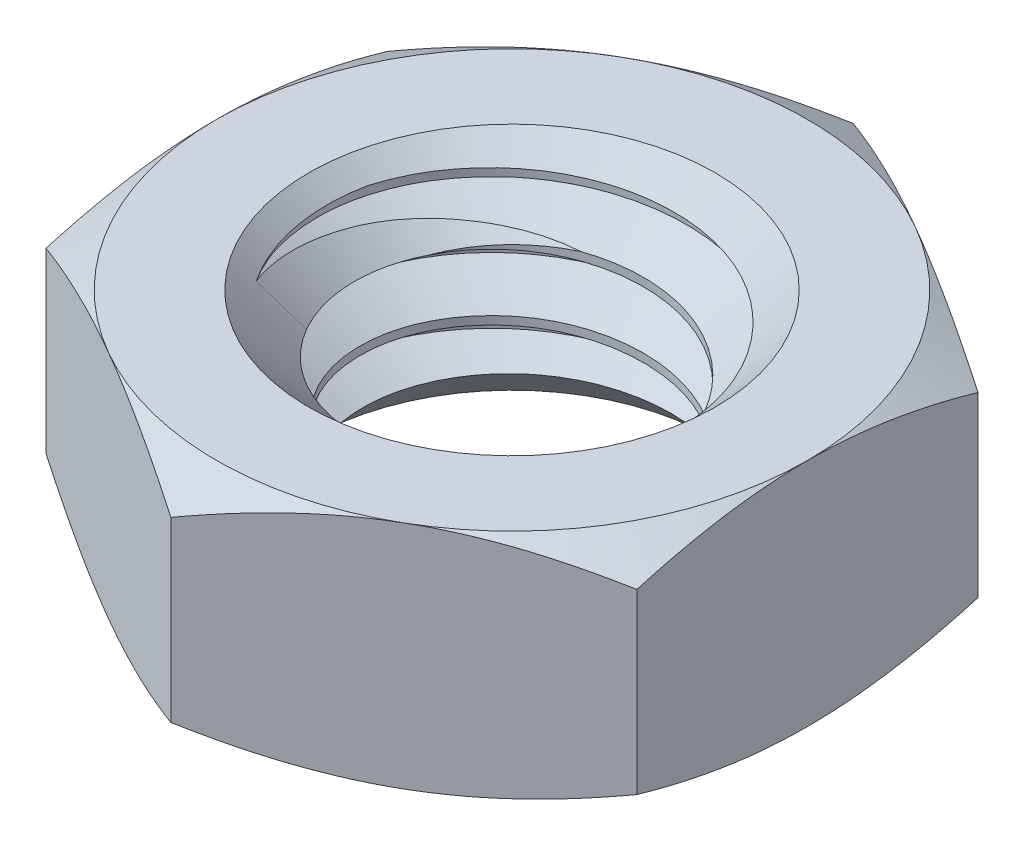
SolidWorks part; units mm, degrees
ref_plane "Front Plane" through (0, 0, 0) normal (0, 0, 1) x (1, 0, 0)
ref_plane "Top Plane" through (0, 0, 0) normal (0, 1, 0) x (1, 0, 0)
ref_plane "Right Plane" through (0, 0, 0) normal (1, 0, 0) x (0, 0, -1)
sketch "Sketch1" plane through (0, 0, 0) normal (0, 0, 1) x (1, 0, 0)
  line L0 (0, -2.4765) -> (0, 2.4765) construction
  line L1 (3.9688, 2.4765) -> (-3.9688, 2.4765) construction
  line L2 (-6.35, -2.4765) -> (6.35, -2.4765) construction
  line L3 (3.9688, 2.4765) -> (3.9687, 1.0654) construction
  point P4 (0, 0)
  point P8 (0, 2.4765)
  point P10 (0, -2.4765)
  dimension "Height" = 4.953
  dimension "Width" = 12.7
  dimension "Thread Dia" = 7.9375
  dimension "Pitch" = 1.4111
sketch "Sketch2" plane through (0, 0, 0) normal (0, 1, 0) x (1, 0, 0)
  line L1 (0, 7.3323) -> (-6.35, 3.6662)
  line L2 (-6.35, 3.6662) -> (-6.35, -3.6662)
  line L3 (-6.35, -3.6662) -> (0, -7.3323)
  line L4 (0, -7.3323) -> (6.35, -3.6662)
  line L5 (6.35, -3.6662) -> (6.35, 3.6662)
  line L6 (6.35, 3.6662) -> (0, 7.3323)
  circle A0 centre (0, 0) radius 6.35 construction
  circle A1 centre (0, 0) radius 3.9688
  point P11 (0, -3.9688)
  point P14 (0, 0)
extrude "Boss-Extrude1" add sketch "Sketch2" along normal up to vertex (2.4765 mm away) and the other way up to vertex (2.4765 mm away) up to point (0, 2.4765, 0) other way up to point (0, -2.4765, 0)
sketch "Sketch3" plane through (0, 0, 0) normal (1, 0, 0) x (0, 0, -1)
  line L0 (-7.3323, 1.9093) -> (-6.35, 2.4765)
  line L1 (-7.3323, 2.4765) -> (-7.3323, -2.4765) construction
  line L2 (-7.3323, 2.4765) -> (-3.6662, 2.4765) construction
  line L3 (-7.3323, -1.9093) -> (-6.35, -2.4765)
  line L4 (-7.3323, -2.4765) -> (-3.6662, -2.4765) construction
  line L5 (-7.3323, 1.9093) -> (-7.3323, 2.4765)
  line L6 (-7.3323, 2.4765) -> (-6.35, 2.4765)
  line L7 (-7.3323, -1.9093) -> (-7.3323, -2.4765)
  line L8 (-7.3323, -2.4765) -> (-6.35, -2.4765)
  line L9 (-6.35, 2.4765) -> (-6.35, -2.4765) construction
  line L10 (-4.3656, 2.4765) -> (-3.9688, 2.4765)
  line L11 (-3.6662, 2.4765) -> (3.6662, 2.4765) construction
  line L12 (-3.9688, 2.4765) -> (-3.9688, 2.0796)
  line L13 (-3.9688, 2.0796) -> (-4.3656, 2.4765)
  line L14 (-4.3656, -2.4765) -> (-3.9687, -2.4765)
  line L15 (-3.6662, -2.4765) -> (3.6662, -2.4765) construction
  line L16 (-3.9687, -2.4765) -> (-3.9688, -2.0796)
  line L17 (-4.3656, -2.4765) -> (-3.9688, -2.0796)
  line L18 (-3.9688, 2.0796) -> (-3.9688, -2.0796) construction
  line L19 (3.9688, 0) -> (-3.9688, 0) construction
  line L22 (0, 2.4765) -> (0, -2.4765) construction
  point P15 (-6.35, 0)
  point P24 (-3.9688, 0)
  dimension "D1" = 30
  dimension "D2" = 4.3656
revolve "Cut-Revolve1" cut sketch "Sketch3" angle 360 about L22
sketch "Sketch4" plane through (0, 2.4765, 0) normal (0, 1, 0) x (1, 0, 0)
  circle A0 centre (0, 0) radius 3.9688 construction
  circle A1 centre (0, 0) radius 3.9688
extrude "Boss-Extrude2" add sketch "Sketch4" against normal up to surface (4.953 mm away) separate body up to face at (0, -2.4765, 4.3656)
sketch "Sketch5" plane through (0, 2.4765, 0) normal (0, 1, 0) x (1, 0, 0)
  circle A0 centre (0, 0) radius 3.9688 construction
  circle A1 centre (0, 0) radius 3.9688
curve "Helix/Spiral1" pitch 1.4111 height 6.3641 radius 3.9688 centre (0, 2.4765, 0) axis (0, -1, 0) start towards (0, 0, 1)
sketch "Sketch6" plane through (0, 0, 0) normal (1, 0, 0) x (0, 0, -1)
  line L0 (-4.1215, 2.3883) -> (-2.8994, 3.0939) construction
  line L1 (-2.8994, 3.0939) -> (-4.1215, 3.7994) construction
  line L2 (-4.1215, 3.7994) -> (-4.1215, 2.3883) construction
  line L3 (-3.0522, 3.1821) -> (-3.0522, 3.0057) construction
  line L4 (-3.9688, 3.7112) -> (-3.9688, 2.4765) construction
  line L5 (-4.1215, 3.0939) -> (-3.9688, 3.0939) construction
  line L6 (-3.0522, 3.0939) -> (-2.8994, 3.0939) construction
  line L7 (-4.0451, 3.0939) -> (-4.0451, 2.4324) construction
  line L8 (-4.0451, 2.4324) -> (-4.0451, 3.7553)
  line L9 (-4.0451, 3.7553) -> (-3.0522, 3.1821)
  line L10 (-3.0522, 3.1821) -> (-3.0522, 3.0057)
  line L11 (-3.0522, 3.0057) -> (-4.0451, 2.4324)
  dimension "D1" = 1.4111
  dimension "D2" = 0.1764
sweep "Cut-Sweep1" cut profiles "Sketch6" path "Helix/Spiral1" align with end faces yes
sketch "Sketch7" plane through (0, 0, 0) normal (1, 0, 0) x (0, 0, -1)
  line L0 (-4.3656, 2.4765) -> (-2.3813, 0.4921)
  line L2 (-4.3656, 2.4765) -> (0, 2.4765)
  line L3 (-4.3656, 2.4765) -> (-3.9688, 2.4765) construction
  line L4 (-4.3656, -2.4765) -> (0, -2.4765)
  line L5 (-4.3656, -2.4765) -> (-3.9687, -2.4765) construction
  line L6 (-4.3656, -2.4765) -> (-2.3813, -0.4921)
  line L7 (-4.3656, -2.4765) -> (-3.9688, -2.0796) construction
  line L8 (0, -2.4765) -> (0, 2.4765) construction
  line L9 (0, -2.4765) -> (0, 2.4765) construction
  line L12 (-2.3813, 0.4921) -> (0, 0.4921)
  line L13 (0, 0.4921) -> (0, 2.4765)
  line L14 (-3.9688, 2.0796) -> (-4.3656, 2.4765) construction
  line L15 (-2.3813, -0.4921) -> (0, -0.4921)
  line L16 (0, -0.4921) -> (0, -2.4765)
  dimension "D1" = 2.3813
revolve "Revolve1" add sketch "Sketch7" angle 360 about L9
sketch "Sketch8" plane through (0, 2.4765, 0) normal (0, 1, 0) x (1, 0, 0)
  circle A0 centre (0, 0) radius 4.3656 construction
  circle A1 centre (0, 0) radius 4.3656
extrude "Boss-Extrude3" add sketch "Sketch8" against normal up to surface (4.953 mm away) up to face at (0, -2.4765, 4.3656)
combine bodies "Combine1" operation type subtract main body 109 bodies to subtract 108
equation "\"D2@Sketch3\"=\"Thread Dia@Sketch1\"*.55"
equation "\"D4@Helix/Spiral1\"=\"Pitch@Sketch1\""
equation "\"D3@Helix/Spiral1\"=\"Height@Sketch1\"+\"Pitch@Sketch1\""
equation "\"D1@Sketch6\"=\"Pitch@Sketch1\""
equation "\"D2@Sketch6\"=\"Pitch@Sketch1\"/8"
equation "\"D1@Sketch7\"=\"Thread Dia@Sketch1\"*.3"
